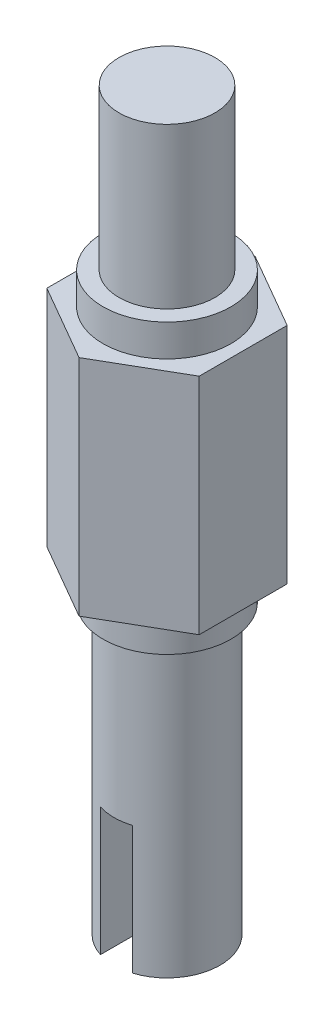
SolidWorks part; units mm, degrees
ref_plane "Front Plane" through (0, 0, 0) normal (0, 0, 1) x (1, 0, 0)
ref_plane "Top Plane" through (0, 0, 0) normal (0, 1, 0) x (1, 0, 0)
ref_plane "Right Plane" through (0, 0, 0) normal (1, 0, 0) x (0, 0, -1)
sketch "Sketch1" plane through (0, 0, 0) normal (0, 1, 0) x (1, 0, 0)
  line L1 (4.7625, -2.7496) -> (4.7625, 2.7496)
  line L2 (4.7625, 2.7496) -> (0, 5.4993)
  line L3 (0, 5.4993) -> (-4.7625, 2.7496)
  line L4 (-4.7625, 2.7496) -> (-4.7625, -2.7496)
  line L5 (-4.7625, -2.7496) -> (0, -5.4993)
  line L6 (0, -5.4993) -> (4.7625, -2.7496)
  circle A0 centre (0, 0) radius 4.7625 construction
  dimension "D1" = 9.525
extrude "Boss-Extrude1" add sketch "Sketch1" along normal blind 14
sketch "Sketch4" plane through (0, 0, 0) normal (0, -1, 0) x (1, 0, 0)
  line L0 (-1, 3.1601) -> (-1, 1.1601)
  line L1 (-1, 1.1601) -> (1, 1.1601)
  line L2 (1, 1.1601) -> (1, 3.1601)
  arc A0 (-1, 3.1601) -> (1, 3.1601) centre (0, 0) ccw
  circle A1 centre (0, 0) radius 4
  arc A2 (1, 3.1601) -> (-1, 3.1601) centre (0, 0) ccw construction
  circle A3 centre (0, 0) radius 3.3145
  dimension "D3" = 8
  dimension "D1" = 2
  dimension "D2" = 2
extrude "Boss-Extrude2" add sketch "Sketch4" along normal blind 2 contours A1 A0 | L0 A0 L2 L1 | L2 A0 L0 L1 region at (0, 0, 2.2123) region at (0, 0, -0.3071) region at (-3.8869, 0, 0)
extrude "Boss-Extrude3" add sketch "Sketch4<7>" along normal blind 12 contours A0 L2 L1 L0 | A3
sketch "Sketch4<7>" plane through (0, 0, 0) normal (0, -1, 0) x (1, 0, 0) same geometry as "Sketch4"
sketch "Sketch5" plane through (0, 14, 0) normal (0, 1, 0) x (1, 0, 0)
  circle A0 centre (0, 0) radius 4
  circle A1 centre (0, 0) radius 3
  dimension "D1" = 8
  dimension "D2" = 6
extrude "Boss-Extrude5" add sketch "Sketch5" along normal blind 2 contours A1 | A0 A1 region at (-3.8869, 14, 0) region at (0, 14, 0)
extrude "Boss-Extrude6" add sketch "Sketch5<4>" along normal offset from surface (12 mm away) 10 contours A1 region at (0, 14, 0) up to face at (0, 16, 4) offset beyond the face yes
sketch "Sketch5<4>" plane through (0, 14, 0) normal (0, 1, 0) x (1, 0, 0) same geometry as "Sketch5"
extrude "Boss-Extrude7" add sketch "Sketch4<13>" along normal offset from surface (20 mm away) 8 contours A0 L2 L1 L0 up to face at (0, -12, -3.3145) offset beyond the face yes
sketch "Sketch4<13>" plane through (0, 0, 0) normal (0, -1, 0) x (1, 0, 0) same geometry as "Sketch4"
